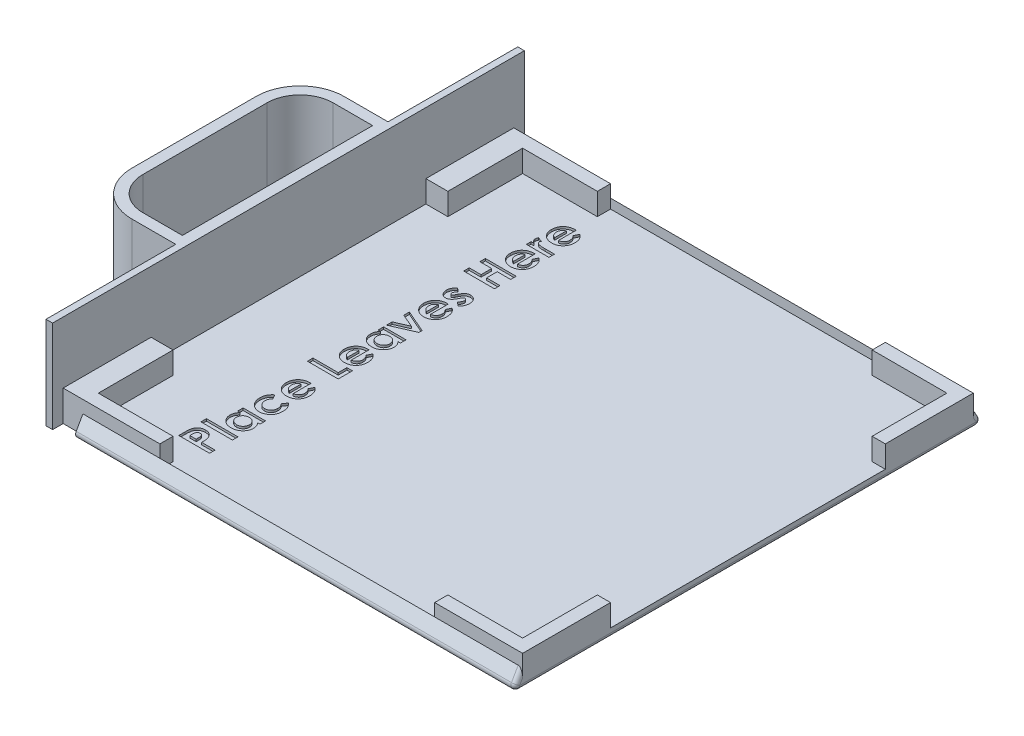
SolidWorks part; units mm, degrees
ref_plane "Front Plane" through (0, 0, 0) normal (0, 0, 1) x (1, 0, 0)
ref_plane "Top Plane" through (0, 0, 0) normal (0, 1, 0) x (1, 0, 0)
ref_plane "Right Plane" through (0, 0, 0) normal (1, 0, 0) x (0, 0, -1)
sketch "Sketch1" plane through (0, 0, 0) normal (0, 1, 0) x (1, 0, 0)
  line L1 (-51.25, -51.25) -> (51.25, -51.25)
  line L2 (-51.25, -51.25) -> (-51.25, 51.25)
  line L3 (-51.25, 51.25) -> (51.25, 51.25)
  line L4 (51.25, -51.25) -> (51.25, 51.25)
  line L5 (-51.25, -51.25) -> (51.25, 51.25) construction
  line L6 (-51.25, 51.25) -> (51.25, -51.25) construction
  point P0 (0, 0)
  dimension "D1" = 102.5
  dimension "D2" = 102.5
extrude "Boss-Extrude1" add sketch "Sketch1" along normal blind 2
sketch "Sketch3" plane through (0, 2, 0) normal (0, 1, 0) x (1, 0, 0)
  line L0 (0, 0) -> (77.4396, 0) construction
  line L1 (51.25, 51.25) -> (31.25, 51.25)
  line L2 (51.25, 51.25) -> (51.25, 31.25)
  line L3 (51.25, 31.25) -> (31.25, 31.25)
  line L4 (31.25, 51.25) -> (31.25, 31.25)
  line L5 (0, 0) -> (0, -79.7735) construction
  line L6 (51.25, -31.25) -> (31.25, -31.25)
  line L7 (31.25, -51.25) -> (31.25, -31.25)
  line L8 (51.25, -51.25) -> (31.25, -51.25)
  line L9 (51.25, -51.25) -> (51.25, -31.25)
  line L10 (-51.25, -51.25) -> (-51.25, -31.25)
  line L11 (-51.25, -51.25) -> (-31.25, -51.25)
  line L12 (-31.25, -51.25) -> (-31.25, -31.25)
  line L13 (-51.25, -31.25) -> (-31.25, -31.25)
  line L14 (-51.25, 31.25) -> (-31.25, 31.25)
  line L15 (-31.25, 51.25) -> (-31.25, 31.25)
  line L16 (-51.25, 51.25) -> (-31.25, 51.25)
  line L17 (-51.25, 51.25) -> (-51.25, 31.25)
  dimension "D1" = 20
  dimension "D2" = 20
extrude "Boss-Extrude2" add sketch "Sketch3" along normal blind 5
sketch "Sketch4" plane through (0, 2, 0) normal (0, 1, 0) x (1, 0, 0)
  line L1 (-48.25, 48.25) -> (48.25, 48.25)
  line L2 (-48.25, 48.25) -> (-48.25, -48.25)
  line L3 (-48.25, -48.25) -> (48.25, -48.25)
  line L4 (48.25, 48.25) -> (48.25, -48.25)
  line L5 (-48.25, 48.25) -> (48.25, -48.25) construction
  line L6 (-48.25, -48.25) -> (48.25, 48.25) construction
  point P0 (0, 0)
  dimension "D1" = 96.5
  dimension "D2" = 96.5
extrude "Cut-Extrude1" cut sketch "Sketch4" along normal through all
sketch "Sketch5" plane through (0, 2, 0) normal (0, 1, 0) x (1, 0, 0)
  line L1 (-40, 40) -> (40, 40)
  line L2 (-40, 40) -> (-40, -40)
  line L3 (-40, -40) -> (40, -40)
  line L4 (40, 40) -> (40, -40)
  line L5 (-40, 40) -> (40, -40) construction
  line L6 (-40, -40) -> (40, 40) construction
  point P0 (0, 0)
  dimension "D1" = 80
extrude "Cut-Extrude2" [suppressed] cut sketch "Sketch5" against normal blind 10
sketch "Sketch6" plane through (-51.25, 0, 0) normal (-1, 0, 0) x (0, 0, 1)
  line L0 (51.25, 7) -> (51.25, 0) construction
  line L1 (-51.25, 0) -> (51.25, 0)
  line L2 (-51.25, 0) -> (-51.25, 2)
  line L3 (-51.25, 2) -> (51.25, 2)
  line L4 (51.25, 0) -> (51.25, 2)
  line L5 (-31.25, 2) -> (31.25, 2) construction
extrude "Boss-Extrude3" add sketch "Sketch6" along normal blind 2
sketch "Sketch8" plane through (-53.25, 0, 0) normal (-1, 0, 0) x (0, 0, 1)
  line L0 (51.25, 2) -> (-51.25, 2) construction
  line L1 (-53.65, 0) -> (53.65, 0)
  line L2 (-53.65, 0) -> (-53.65, 21)
  line L3 (-53.65, 21) -> (53.65, 21)
  line L4 (53.65, 0) -> (53.65, 21)
  line L7 (-51.25, 0) -> (51.25, 0) construction
  point P4 (0, 0)
  point P7 (0, 2)
  dimension "D1" = 107.3
  dimension "D2" = 21
extrude "Boss-Extrude5" add sketch "Sketch8" along normal blind 1.5
sketch "Sketch10" plane through (-54.75, 0, 0) normal (-1, 0, 0) x (0, 0, 1)
  line L0 (-53.65, 0) -> (53.65, 0) construction
  line L1 (-24.136, 0) -> (24.136, 0)
  line L2 (-24.136, 0) -> (-24.136, 21)
  line L3 (-24.136, 21) -> (24.136, 21)
  line L4 (24.136, 0) -> (24.136, 21)
  line L5 (53.65, 21) -> (-53.65, 21) construction
extrude "Boss-Extrude6" add sketch "Sketch10" along normal blind 20
fillet "Fillet1" radius 10 2 edges at (-74.75, 10.5, 24.136) (-74.75, 10.5, -24.136)
shell "Shell1" thickness 2.5 removed face at (-43.7602, 0, 0) removed face at (-60.8642, 21, 0)
chamfer "Chamfer1" [suppressed] distance 10 angle 45
sketch "Sketch11" [suppressed] plane through (-51.25, 0, 0) normal (-1, 0, 0) x (0, 0, 1)
  line L0 (31.25, 7) -> (51.25, 7) construction
  line L1 (31.25, 2) -> (51.25, 2)
  line L2 (31.25, 2) -> (31.25, 7)
  line L3 (31.25, 7) -> (51.25, 7)
  line L4 (51.25, 2) -> (51.25, 7)
  line L5 (-51.25, 7) -> (-31.25, 7) construction
  line L6 (-31.25, 2) -> (-51.25, 2)
  line L7 (-31.25, 2) -> (-31.25, 7)
  line L8 (-31.25, 7) -> (-51.25, 7)
  line L9 (-51.25, 2) -> (-51.25, 7)
  line L10 (-51.25, 7) -> (-51.25, 2) construction
  line L11 (51.25, 7) -> (51.25, 2) construction
sketch "Sketch12" plane through (0, 2, 0) normal (0, 1, 0) x (1, 0, 0)
  line L0 (-28.75, -45.9426) -> (-28.75, 46.1284) construction
  line L1 (31.25, 51.25) -> (31.25, 48.25) construction
  text T0 "Place Leaves Here" font "Century Gothic" height 7
  dimension "D1" = 60
extrude "Cut-Extrude3" cut sketch "Sketch12" against normal blind 0.5
sketch "Sketch13" plane through (51.25, 0, 0) normal (1, 0, 0) x (0, 0, -1)
  line L0 (-51.25, 0) -> (-53.65, 0)
  line L1 (-53.65, 0) -> (-51.25, 4.1569)
  line L2 (-51.25, 7) -> (-51.25, 0) construction
  line L3 (-51.25, 4.1569) -> (-51.25, 0)
  line L4 (0, 0) -> (0, 16.5802) construction
  line L5 (-51.25, 0) -> (51.25, 0) construction
  line L6 (53.65, 0) -> (51.25, 4.1569)
  line L7 (51.25, 0) -> (53.65, 0)
  line L8 (51.25, 4.1569) -> (51.25, 0)
  dimension "D1" = 2.4
  dimension "D2" = 60
extrude "Boss-Extrude8" add sketch "Sketch13" against normal blind 100
fillet "Fillet2" [suppressed] radius 1
fillet "Fillet3" radius 1 5 edges at (51.25, 2.0785, 52.45) (1.25, 0, 53.65) (51.25, 0, 0) (51.25, 2.0785, -52.45) (1.25, 0, -53.65)
extrude "Boss-Extrude9" [suppressed] add sketch "Sketch11" along normal up to next
sketch "Sketch14" plane through (-51.25, 0, 0) normal (-1, 0, 0) x (0, 0, 1)
  line L1 (-51.25, 2) -> (-31.25, 2)
  line L2 (-51.25, 2) -> (-51.25, 7)
  line L3 (-51.25, 7) -> (-31.25, 7)
  line L4 (-31.25, 2) -> (-31.25, 7)
  line L5 (31.25, 7) -> (51.25, 7)
  line L6 (31.25, 7) -> (31.25, 2)
  line L7 (31.25, 2) -> (51.25, 2)
  line L8 (51.25, 7) -> (51.25, 2)
extrude "Boss-Extrude10" add sketch "Sketch14" along normal up to next
